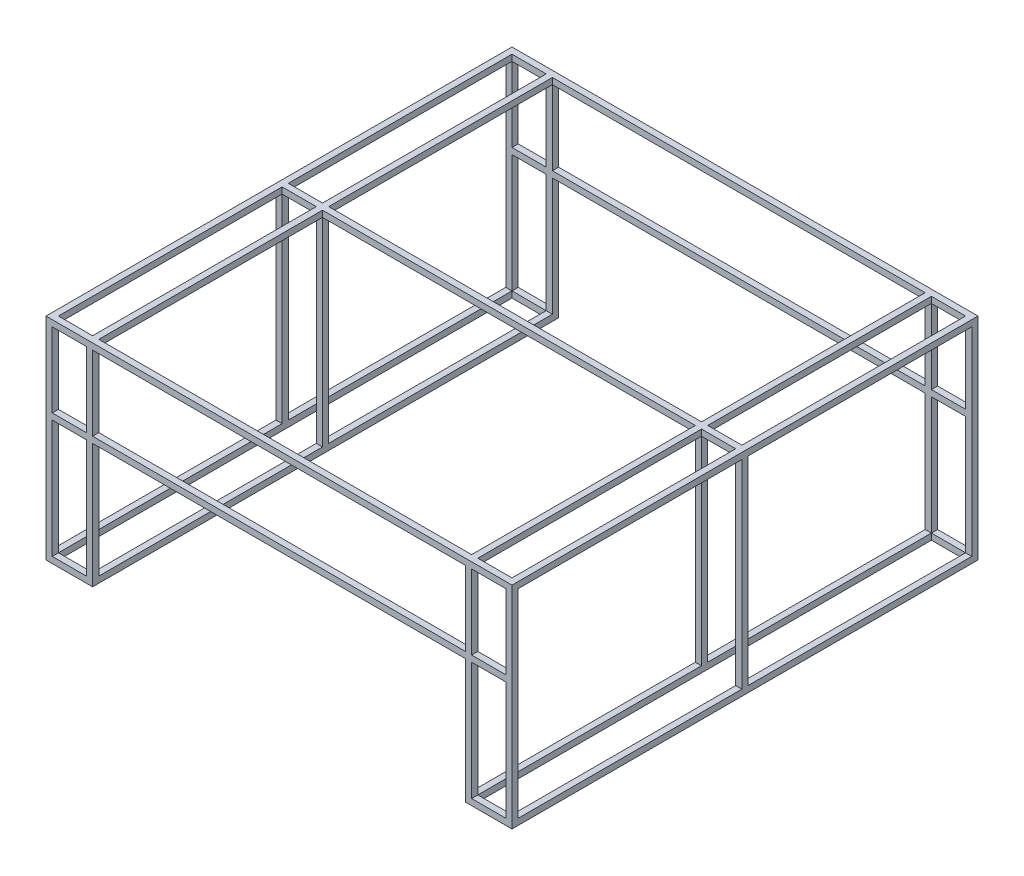
SolidWorks part; units mm, degrees
ref_plane "Front Plane" through (0, 0, 0) normal (0, 0, 1) x (1, 0, 0)
ref_plane "Top Plane" through (0, 0, 0) normal (0, 1, 0) x (1, 0, 0)
ref_plane "Right Plane" through (0, 0, 0) normal (1, 0, 0) x (0, 0, -1)
sketch "Sketch1" plane through (0, 0, 0) normal (0, 1, 0) x (1, 0, 0)
  line L0 (730, 730) -> (730, -730)
  line L1 (750, 750) -> (600, 750)
  line L2 (750, 750) -> (750, -750)
  line L3 (750, -750) -> (600, -750)
  line L4 (600, 750) -> (600, -750)
  line L5 (730, -730) -> (620, -730)
  line L6 (620, 730) -> (620, -730)
  line L7 (730, 730) -> (620, 730)
  point P4 (750, 0)
  dimension "D1" = 600
  dimension "D2" = 150
  dimension "D3" = 1500
  dimension "D4" = 20
extrude "Boss-Extrude1" add sketch "Sketch1" along normal blind 20
sketch "Sketch2" plane through (0, 20, 0) normal (0, 1, 0) x (1, 0, 0)
  line L1 (620, 730) -> (600, 730)
  line L2 (620, 730) -> (620, 750)
  line L3 (620, 750) -> (600, 750)
  line L4 (600, 730) -> (600, 750)
  line L5 (730, 730) -> (750, 730)
  line L6 (730, 730) -> (730, 750)
  line L7 (730, 750) -> (750, 750)
  line L8 (750, 730) -> (750, 750)
  line L9 (600, -750) -> (620, -750)
  line L10 (600, -750) -> (600, -730)
  line L11 (600, -730) -> (620, -730)
  line L12 (620, -750) -> (620, -730)
  line L13 (730, -730) -> (750, -730)
  line L14 (730, -730) -> (730, -750)
  line L15 (730, -750) -> (750, -750)
  line L16 (750, -730) -> (750, -750)
extrude "Boss-Extrude2" add sketch "Sketch2" along normal blind 640
sketch "Sketch3" plane through (0, 660, 0) normal (0, 1, 0) x (1, 0, 0)
  line L0 (620, 730) -> (620, -730)
  line L1 (600, 750) -> (750, 750)
  line L2 (600, 750) -> (600, -750)
  line L3 (600, -750) -> (750, -750)
  line L4 (750, 750) -> (750, -750)
  line L5 (620, -730) -> (730, -730)
  line L6 (730, 730) -> (730, -730)
  line L7 (620, 730) -> (730, 730)
  dimension "D1" = 20
extrude "Boss-Extrude3" add sketch "Sketch3" along normal blind 20
sketch "Sketch4" plane through (0, 0, 0) normal (0, -1, 0) x (1, 0, 0)
  line L0 (730, 730) -> (730, -730) construction
  line L1 (730, 10) -> (750, 10)
  line L2 (730, 10) -> (730, -10)
  line L3 (730, -10) -> (750, -10)
  line L4 (750, 10) -> (750, -10)
  line L5 (750, 750) -> (750, -750) construction
  line L6 (750, -750) -> (600, -750) construction
  line L7 (600, -750) -> (600, 750) construction
  line L8 (600, -10) -> (620, -10)
  line L9 (600, -10) -> (600, 10)
  line L10 (600, 10) -> (620, 10)
  line L11 (620, -10) -> (620, 10)
  line L12 (620, -730) -> (620, 730) construction
  dimension "D1" = 20
  dimension "D2" = 740
extrude "Boss-Extrude4" add sketch "Sketch4" against normal up to surface (660 mm away) up to face at (610, 660, 0)
sketch "Sketch5" plane through (600, 0, 0) normal (-1, 0, 0) x (0, 0, 1)
  line L0 (-750, 680) -> (-750, 0) construction
  line L1 (-750, 420) -> (-730, 420)
  line L2 (-750, 420) -> (-750, 400)
  line L3 (-750, 400) -> (-730, 400)
  line L4 (-730, 420) -> (-730, 400)
  line L5 (-730, 660) -> (-730, 20) construction
  line L6 (-750, 0) -> (750, 0) construction
  line L7 (0, -82.5) -> (0, 82.5) construction
  line L8 (-730, 660) -> (-750, 660)
  line L9 (-730, 660) -> (-730, 680)
  line L10 (-730, 680) -> (-750, 680)
  line L11 (-750, 660) -> (-750, 680)
  line L12 (750, 420) -> (750, 400)
  line L13 (750, 400) -> (730, 400)
  line L14 (730, 420) -> (730, 400)
  line L15 (750, 420) -> (730, 420)
  line L16 (730, 680) -> (750, 680)
  line L17 (750, 660) -> (750, 680)
  line L18 (730, 660) -> (750, 660)
  line L19 (730, 660) -> (730, 680)
  line L20 (-750, 680) -> (750, 680) construction
  line L21 (-10, 660) -> (10, 660)
  line L22 (-10, 660) -> (-10, 680)
  line L23 (-10, 680) -> (10, 680)
  line L24 (10, 660) -> (10, 680)
  line L25 (10, 660) -> (10, 20) construction
  dimension "D1" = 20
  dimension "D2" = 400
extrude "Boss-Extrude5" add sketch "Sketch5" along normal blind 600 and the other way up to surface (130 mm away) other way up to face at (730, 340, -740)
mirror "Mirror1" about plane through (0, 0, 0) normal (1, 0, 0) of bodies 105
